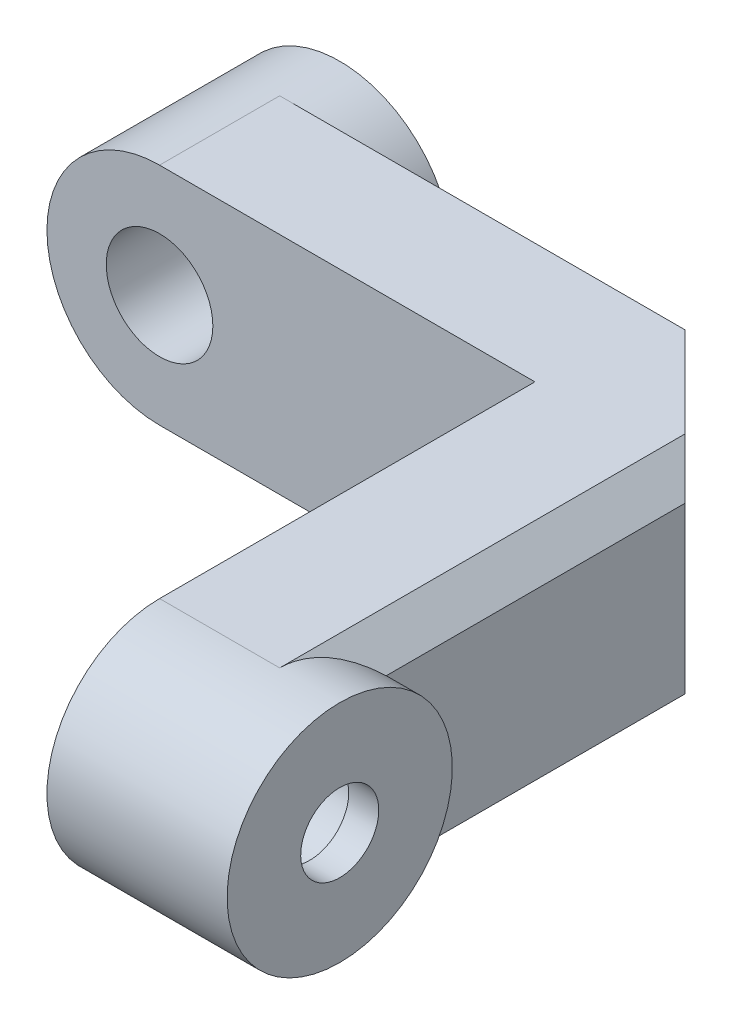
SolidWorks part; units mm, degrees
ref_plane "Front Plane" through (0, 0, 0) normal (0, 0, 1) x (1, 0, 0)
ref_plane "Top Plane" through (0, 0, 0) normal (0, 1, 0) x (1, 0, 0)
ref_plane "Right Plane" through (0, 0, 0) normal (1, 0, 0) x (0, 0, -1)
sketch "Sketch3" plane through (0, 0, 0) normal (0, 0, 1) x (1, 0, 0)
  line L1 (-25, 20) -> (25, 20)
  line L2 (-25, 20) -> (-25, -20)
  line L3 (-25, -20) -> (25, -20)
  line L4 (25, 20) -> (25, -20)
  line L5 (-25, 20) -> (25, -20) construction
  line L6 (-25, -20) -> (25, 20) construction
  circle A0 centre (0, 0) radius 3.55
  dimension "D1" = 40
  dimension "D3" = 7.1
  dimension "D2" = 50
extrude "Boss-Extrude3" add sketch "Sketch3" along normal blind 10
sketch "Sketch4" plane through (25, 0, 0) normal (1, 0, 0) x (0, 0, -1)
  line L1 (-50, -20) -> (0, -20)
  line L2 (-50, -20) -> (-50, 20)
  line L3 (-50, 20) -> (0, 20)
  line L4 (0, -20) -> (0, 20)
  line L5 (-50, -20) -> (0, 20) construction
  line L6 (-50, 20) -> (0, -20) construction
  line L7 (-10, -20) -> (-10, 20) construction
  circle A0 centre (-35, 0) radius 3.55
  point P0 (-35, 0)
  point P8 (0, 0)
  point P10 (0, 0)
  point P13 (-35, 0)
  dimension "D2" = 25
  dimension "D3" = 7.1
  dimension "D1" = 40
  dimension "D4" = 50
extrude "Boss-Extrude4" add sketch "Sketch4" along normal blind 10
sketch "Sketch5" plane through (0, 0, 0) normal (0, 0, -1) x (-1, 0, 0)
  line L0 (0, 7.5) -> (-35, 7.5)
  line L1 (-35, -20) -> (-35, 20) construction
  line L2 (-35, 7.5) -> (-35, -7.5)
  line L3 (-35, -7.5) -> (0, -7.5)
  arc A0 (0, -7.5) -> (0, 7.5) centre (0, 0) ccw
  dimension "D1" = 15
extrude "Cut-Extrude1" cut sketch "Sketch5" against normal through all both and the other way through all flip side to cut
sketch "Sketch6" plane through (35, 0, 0) normal (1, 0, 0) x (0, 0, -1)
  line L4 (-35, 7.5) -> (0, 7.5)
  line L5 (0, 7.5) -> (0, -7.5)
  line L6 (0, -7.5) -> (-35, -7.5)
  arc A1 (-35, 7.5) -> (-35, -7.5) centre (-35, 0) ccw
extrude "Cut-Extrude2" cut sketch "Sketch6" against normal through all both flip side to cut
sketch "Sketch7" plane through (35, 0, 0) normal (1, 0, 0) x (0, 0, -1)
  circle A1 centre (-35, 0) radius 2.6
  circle A2 centre (-35, 0) radius 7.5
extrude "Boss-Extrude5" add sketch "Sketch7" along normal blind 2
sketch "Sketch8" plane through (0, 0, 0) normal (0, 0, -1) x (-1, 0, 0)
  circle A0 centre (0, 0) radius 7.5
  circle A1 centre (0, 0) radius 2.6
extrude "Boss-Extrude6" add sketch "Sketch8" along normal blind 2
chamfer "Chamfer1" distance 10 angle 45 1 edges at (35, 0, 0)
chamfer "Chamfer2" distance 2 angle 45 4 edges at (35, -7.5, 22.5) (35, 7.5, 22.5) (12.5, -7.5, 0) (12.5, 7.5, 0)
